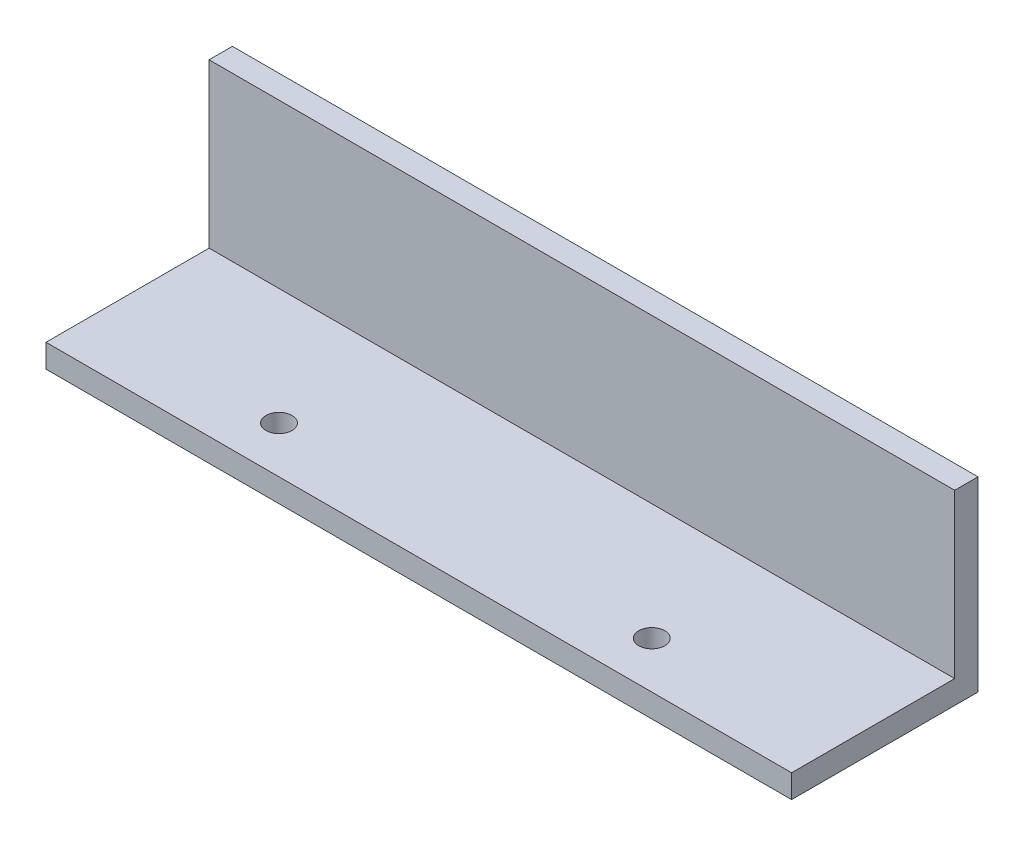
SolidWorks part; units mm, degrees
ref_plane "Front Plane" through (0, 0, 0) normal (0, 0, 1) x (1, 0, 0)
ref_plane "Top Plane" through (0, 0, 0) normal (0, 1, 0) x (1, 0, 0)
ref_plane "Right Plane" through (0, 0, 0) normal (1, 0, 0) x (0, 0, -1)
sketch "Sketch1" plane through (0, 0, 0) normal (0, 1, 0) x (1, 0, 0)
  line L1 (0, 0) -> (101.6, 0)
  line L2 (0, 0) -> (0, 50.8)
  line L3 (0, 50.8) -> (101.6, 50.8)
  line L4 (101.6, 0) -> (101.6, 50.8)
extrude "Boss-Extrude1" add sketch "Sketch1" along normal blind 3.175
sketch "Sketch2" plane through (0, 0, 0) normal (0, -1, 0) x (1, 0, 0)
  line L0 (101.6, 0) -> (101.6, -50.8) construction
  line L1 (0, 0) -> (101.6, 0)
  line L2 (0, 0) -> (0, -5.5321)
  line L3 (0, -5.5321) -> (101.6, -5.5321)
  line L4 (101.6, 0) -> (101.6, -5.5321)
sketch "Sketch3" plane through (0, 3.175, 0) normal (0, 1, 0) x (1, 0, 0)
  line L1 (0, 50.8) -> (101.6, 50.8)
  line L2 (0, 50.8) -> (0, 47.625)
  line L3 (0, 47.625) -> (101.6, 47.625)
  line L4 (101.6, 50.8) -> (101.6, 47.625)
extrude "Boss-Extrude2" add sketch "Sketch3" along normal blind 22.225
sketch "Sketch4" plane through (0, 0, 0) normal (0, -1, 0) x (-1, 0, 0)
  circle A0 centre (-25.4, 31.75) radius 1.778
  circle A1 centre (-76.2, 31.75) radius 1.778
  point P0 (-25.4, 31.75)
  point P1 (-76.2, 31.75)
extrude "Cut-Extrude1" cut sketch "Sketch4" against normal through all contours A0
extrude "Cut-Extrude2" cut sketch "Sketch4<3>" against normal blind 22.225
sketch "Sketch4<3>" plane through (0, 0, 0) normal (0, -1, 0) x (-1, 0, 0) same geometry as "Sketch4"
sketch "Sketch7" plane through (0, 0, 0) normal (0, 0, 1) x (1, 0, 0)
  line L1 (101.6, 0) -> (0, 0)
  line L2 (101.6, 0) -> (101.6, 3.175)
  line L3 (101.6, 3.175) -> (0, 3.175)
  line L4 (0, 0) -> (0, 3.175)
extrude "Cut-Extrude3" cut sketch "Sketch7" against normal blind 25.4
